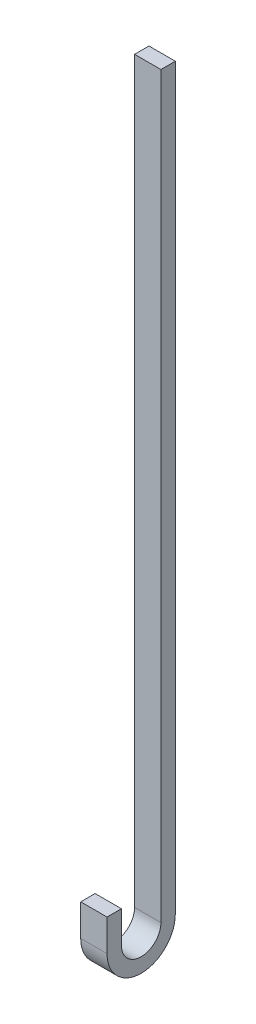
SolidWorks part; units mm, degrees
ref_plane "Front" through (0, 0, 0) normal (0, 0, 1) x (1, 0, 0)
ref_plane "Top" through (0, 0, 0) normal (0, 1, 0) x (1, 0, 0)
ref_plane "Right" through (0, 0, 0) normal (1, 0, 0) x (0, 0, -1)
sketch "Sketch1" plane through (0, 0, 0) normal (1, 0, 0) x (0, 0, -1)
  line L0 (0, 0) -> (0, -33.0425)
  line L1 (71.12, -33.0425) -> (71.12, 736.6)
  line L2 (14.986, 0) -> (14.986, -33.0425)
  line L3 (56.134, -33.0425) -> (56.134, 736.6)
  line L4 (0, 0) -> (14.986, 0)
  line L5 (56.134, 736.6) -> (71.12, 736.6)
  line L7 (82.55, 533.4) -> (-6.35, 533.4) construction
  arc A0 (0, -33.0425) -> (71.12, -33.0425) centre (35.56, -33.0425) ccw
  arc A1 (14.986, -33.0425) -> (56.134, -33.0425) centre (35.56, -33.0425) ccw
  dimension "D1" = 914.4
  dimension "D2" = 71.12
  dimension "D4" = 41.148
  dimension "D5" = 203.2
  dimension "D3" = 14.986
extrude "Boss-Extrude1" add sketch "Sketch1" along normal blind 27.432
